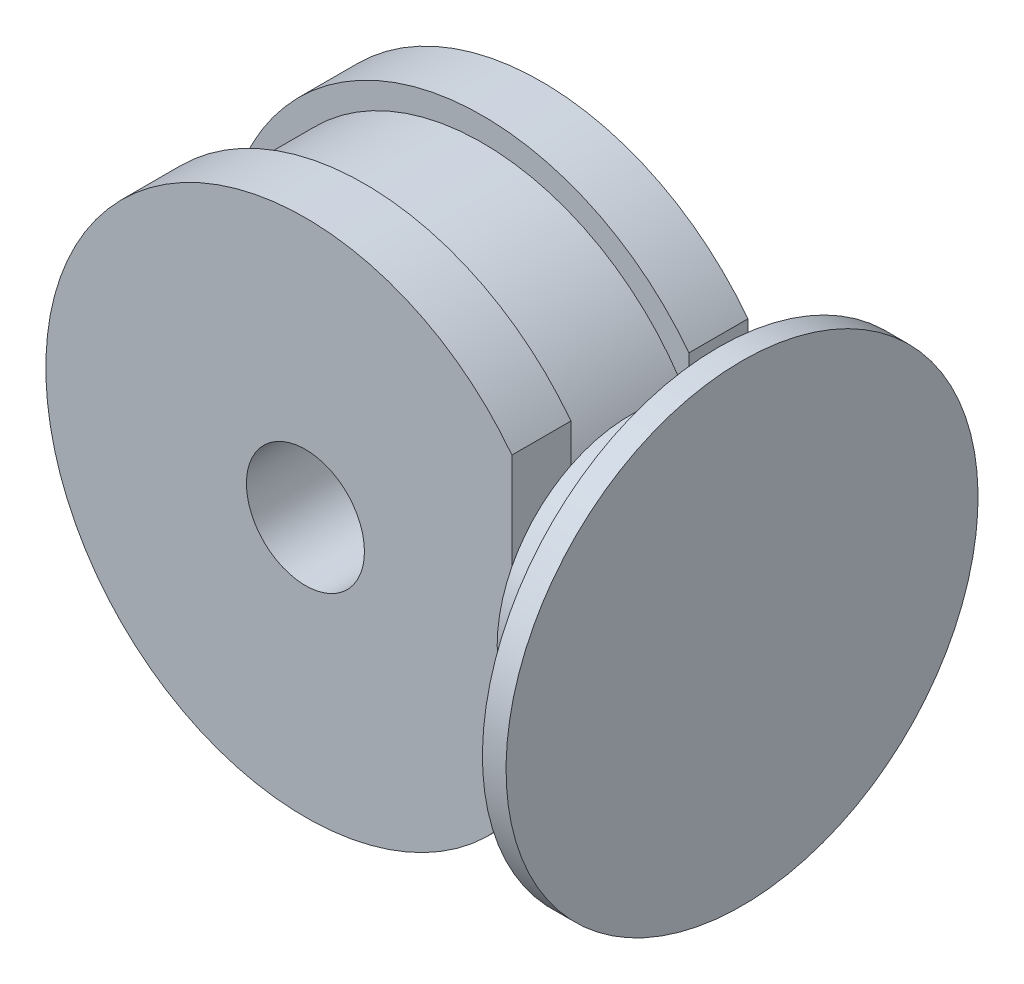
SolidWorks part; units mm, degrees
ref_plane "Plan de face" through (0, 0, 0) normal (0, 0, 1) x (1, 0, 0)
ref_plane "Plan de dessus" through (0, 0, 0) normal (0, 1, 0) x (1, 0, 0)
ref_plane "Plan de droite" through (0, 0, 0) normal (1, 0, 0) x (0, 0, -1)
sketch "Esquisse1" plane through (0, 0, 0) normal (0, 0, 1) x (1, 0, 0)
  circle A0 centre (0, 0) radius 44
  dimension "D1" = 88
extrude "Boss.-Extru.1" add sketch "Esquisse1" along normal blind 10
sketch "Esquisse2" plane through (0, 0, 10) normal (0, 0, 1) x (1, 0, 0)
  circle A0 centre (0, 0) radius 40
  dimension "D1" = 80
extrude "Boss.-Extru.2" add sketch "Esquisse2" along normal blind 20
sketch "Esquisse3" plane through (0, 0, 30) normal (0, 0, 1) x (1, 0, 0)
  circle A0 centre (0, 0) radius 44
extrude "Boss.-Extru.3" add sketch "Esquisse3" along normal blind 10
sketch "Esquisse5" plane through (0, 0, 40) normal (0, 0, 1) x (1, 0, 0)
  line L1 (35, 44.0697) -> (67.4724, 44.0697)
  line L2 (35, 44.0697) -> (35, -50.6619)
  line L3 (35, -50.6619) -> (67.4724, -50.6619)
  line L4 (67.4724, 44.0697) -> (67.4724, -50.6619)
  dimension "D1" = 35
extrude "Enlèv. mat.-Extru.2" cut sketch "Esquisse5" against normal through all
sketch "Esquisse4" plane through (0, 0, 40) normal (0, 0, 1) x (1, 0, 0)
  circle A0 centre (0, 0) radius 10
  dimension "D1" = 20
extrude "Enlèv. mat.-Extru.1" cut sketch "Esquisse4" against normal through all
ref_point "Point1"
sketch "Sketch1" plane through (35, 0, 0) normal (1, 0, 0) x (0, 0, -1)
  circle A0 centre (-20, 0) radius 22.5
extrude "Boss-Extrude1" add sketch "Sketch1" along normal blind 15
sketch "Sketch2" plane through (50, 0, 0) normal (1, 0, 0) x (0, 0, -1)
  circle A0 centre (-20, 0) radius 40
extrude "Boss-Extrude2" add sketch "Sketch2" along normal blind 4
